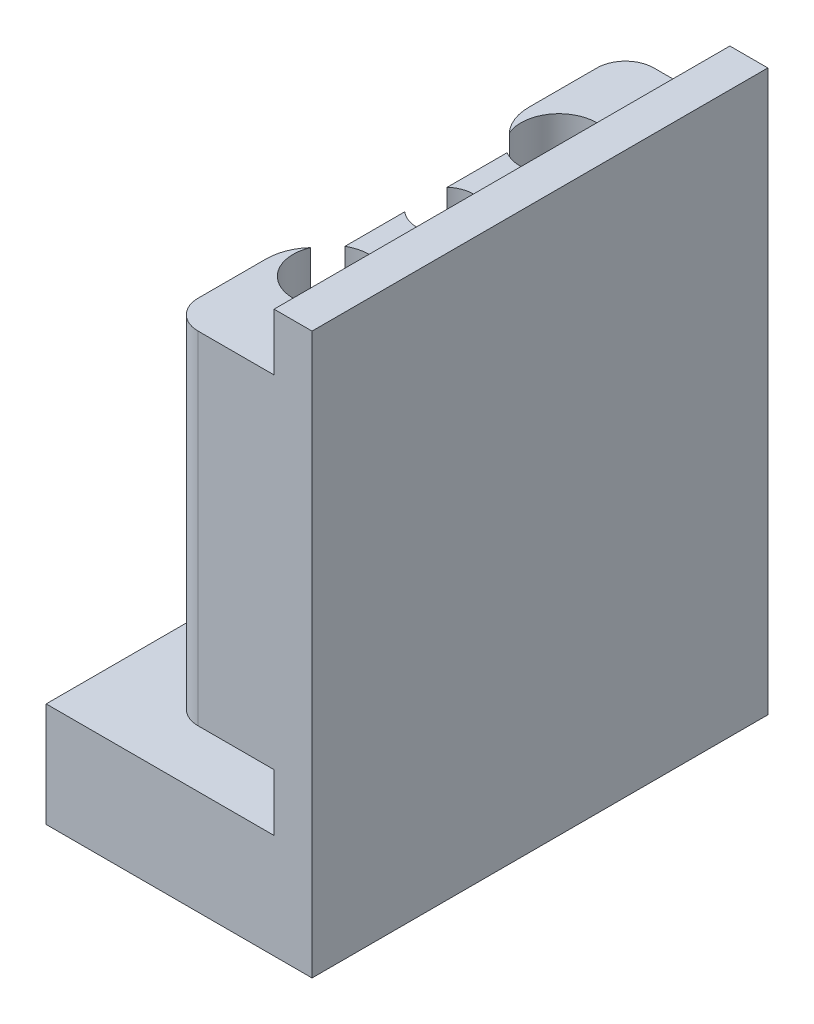
SolidWorks part; units mm, degrees
ref_plane "Front" through (0, 0, 0) normal (0, 0, 1) x (1, 0, 0)
ref_plane "Top" through (0, 0, 0) normal (0, 1, 0) x (1, 0, 0)
ref_plane "Right" through (0, 0, 0) normal (1, 0, 0) x (0, 0, -1)
sketch "Sketch1" plane through (0, 0, 0) normal (0, 1, 0) x (1, 0, 0)
  line L5 (-6, -12) -> (6, -12)
  line L6 (-6, -12) -> (-6, 12)
  line L7 (-6, 12) -> (6, 12)
  line L8 (6, -12) -> (6, 12)
  line L9 (-6, -12) -> (6, 12) construction
  line L10 (-6, 12) -> (6, -12) construction
  point P0 (0, 0)
  dimension "D1" = 12
  dimension "D2" = 24
extrude "Boss-Extrude1" add sketch "Sketch1" along normal blind 5.5
sketch "Sketch2" plane through (0, 0, 0) normal (0, 1, 0) x (1, 0, 0)
  line L0 (6, 12) -> (-6, 12) construction
  line L1 (6, -12) -> (8, -12)
  line L2 (6, -12) -> (6, 12)
  line L3 (6, 12) -> (8, 12)
  line L4 (8, -12) -> (8, 12)
  dimension "D1" = 2
extrude "Boss-Extrude2" add sketch "Sketch2" along normal blind 29.5
sketch "Sketch4" plane through (0, 5.5, 0) normal (0, 1, 0) x (1, 0, 0)
  line L1 (6, -12) -> (0.5, -12)
  line L2 (6, -12) -> (6, 12)
  line L3 (6, 12) -> (0.5, 12)
  line L4 (0.5, -12) -> (0.5, 12)
  line L5 (6, 12) -> (-6, 12) construction
  dimension "D1" = 5.5
extrude "Boss-Extrude4" add sketch "Sketch4" along normal blind 18 from offset 3
sketch "Sketch5" plane through (0.5, 0, 0) normal (-1, 0, 0) x (0, 0, 1)
  line L0 (-12, 26.5) -> (12, 26.5) construction
  line L1 (-4.625, 26.5) -> (4.625, 26.5)
  line L2 (-4.625, 26.5) -> (-4.625, 8.5)
  line L3 (-4.625, 8.5) -> (4.625, 8.5)
  line L4 (4.625, 26.5) -> (4.625, 8.5)
  line L5 (-12, 8.5) -> (12, 8.5) construction
  line L8 (4.625, 26.5) -> (12, 26.5) construction
  line L9 (-4.625, 26.5) -> (-12, 26.5) construction
  dimension "D1" = 9.25
extrude "Cut-Extrude1" cut sketch "Sketch5" against normal blind 1.5
fillet "Fillet1" radius 2.5 2 edges at (0.5, 17.5, 4.625) (0.5, 17.5, -4.625)
sketch "Sketch6" plane through (0, 26.5, 0) normal (0, 1, 0) x (1, 0, 0)
  line L0 (6, 0) -> (2, 0) construction
  line L1 (6, -12) -> (6, 12) construction
  line L2 (2, -4.625) -> (2, 4.625) construction
  line L3 (3, -12) -> (3, -6) construction
  line L4 (0.5, -12) -> (6, -12) construction
  line L5 (3, -6) -> (6, -6) construction
  line L6 (6, 0) -> (3, 0) construction
  circle A0 centre (3, -6) radius 2
  circle A1 centre (3, 6) radius 2
  circle A3 centre (3, 0) radius 1.5
  dimension "D3" = 4
  dimension "D5" = 3
  dimension "D1" = 6
  dimension "D2" = 3
  dimension "D4" = 3
extrude "Cut-Extrude2" cut sketch "Sketch6" against normal through all
fillet "Fillet2" radius 1.5 2 edges at (0.5, 17.5, -12) (0.5, 17.5, 12)
